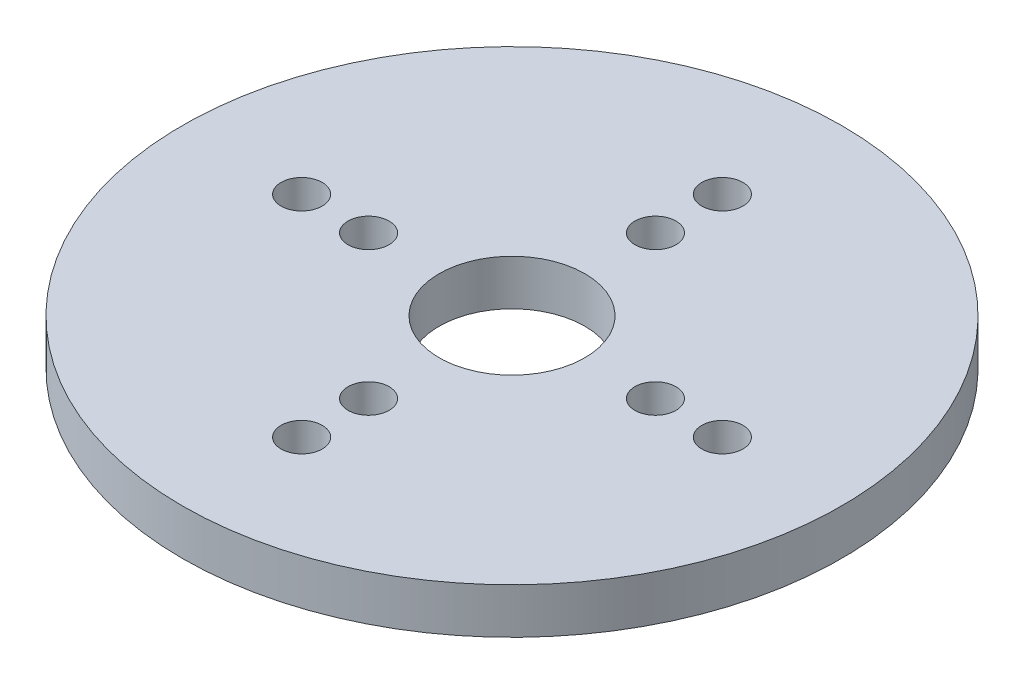
SolidWorks part; units mm, degrees
ref_plane "Front Plane" through (0, 0, 0) normal (0, 0, 1) x (1, 0, 0)
ref_plane "Top Plane" through (0, 0, 0) normal (0, 1, 0) x (1, 0, 0)
ref_plane "Right Plane" through (0, 0, 0) normal (1, 0, 0) x (0, 0, -1)
sketch "Sketch1" plane through (0, 0, 0) normal (0, 1, 0) x (1, 0, 0)
  line L0 (0, -48.2646) -> (0, -8.2647) construction
  line L1 (0, -8.2647) -> (0, 48.2646) construction
  line L2 (0, 0) -> (-42.3088, 0) construction
  line L3 (0, 0) -> (42.3088, 0) construction
  line L4 (0, -8.2647) -> (15, -8.2647) construction
  line L6 (15, -8.2647) -> (22, -8.2647) construction
  line L7 (0, -8.2647) -> (0, -23.2647) construction
  line L8 (0, -23.2647) -> (0, -30.2647) construction
  line L9 (0, -8.2647) -> (-15, -8.2647) construction
  line L10 (-15, -8.2647) -> (-22, -8.2647) construction
  line L11 (0, -8.2647) -> (0, 6.7353) construction
  line L12 (0, 6.7353) -> (0, 13.7353) construction
  line L17 (0, -8.2647) -> (0, -40.6446)
  circle A22 centre (15, -8.2647) radius 2.15
  circle A23 centre (22, -8.2647) radius 2.15
  circle A24 centre (0, -23.2647) radius 2.15
  circle A25 centre (0, -30.2647) radius 2.15
  circle A26 centre (-15, -8.2647) radius 2.15
  circle A27 centre (-22, -8.2647) radius 2.15
  circle A28 centre (0, 6.7353) radius 2.15
  circle A29 centre (0, 13.7353) radius 2.15
  circle A30 centre (0, -8.2647) radius 7.62
  circle A31 centre (0, -8.2647) radius 34.4649
  point P3 (0, 0)
  point P27 (0, -8.2647)
  dimension "D6" = 15
  dimension "D7" = 7
  dimension "D10" = 4
  dimension "D11" = 15.24
  dimension "D8" = 4.3
  dimension "D9" = 4.3
  dimension "D2" = 68.9297
  dimension "D5" = 39.9999
extrude "Boss-Extrude1" add sketch "Sketch1" along normal blind 4.7625 contours A31 A22 A23 A26 A27 A28 A29 A30 A24 A25 region at (-33.49, 0, 8.2647)
